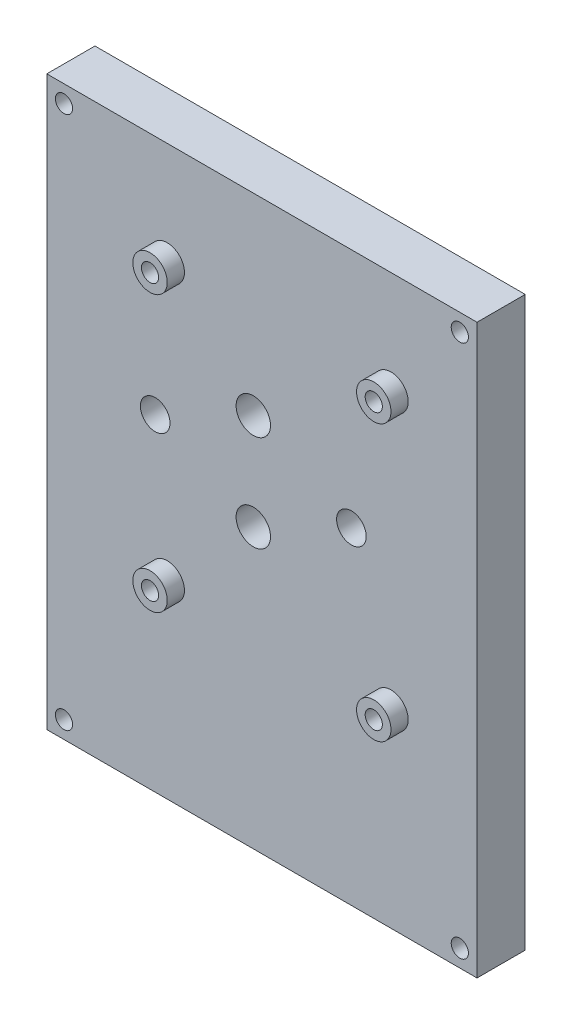
SolidWorks part; units mm, degrees
ref_plane "Oben" through (0, 0, 0) normal (0, 0, 1) x (1, 0, 0)
ref_plane "Vorne" through (0, 0, 0) normal (0, 1, 0) x (1, 0, 0)
ref_plane "Rechts" through (0, 0, 0) normal (1, 0, 0) x (0, 0, -1)
sketch "Skizze1" plane through (0, 0, 0) normal (0, 0, 1) x (1, 0, 0)
  line L0 (0, 17) -> (-7.5, 17)
  line L1 (-7.5, 17) -> (-7.5, -17)
  line L2 (-7.5, -17) -> (17.5, -17)
  line L3 (17.5, -17) -> (17.5, 17)
  line L4 (17.5, 17) -> (0, 17)
  line L5 (-7.5, 17) -> (-17.5, 17)
  line L6 (-17.5, 17) -> (-17.5, -17)
  line L7 (-17.5, -17) -> (-7.5, -17)
  circle A0 centre (14.25, 0) radius 2.15
  circle A1 centre (-14.25, 0) radius 2.15
  circle A2 centre (0, 7) radius 2.5
  circle A3 centre (0, -7) radius 2.5
  point P4 (0, 7)
  point P6 (0, -7)
  dimension "D1" = 4.3
  dimension "D2" = 14.25
  dimension "D14" = 5
  dimension "D15" = 35
  dimension "D3" = 14.25
  dimension "D4" = 7
  dimension "D5" = 7
  dimension "D6" = 10
  dimension "D7" = 7.5
  dimension "D8" = 10
  dimension "D9" = 34
  dimension "D10" = 17.5
  dimension "D11" = 34
  dimension "D12" = 17.5
  dimension "D13" = 25
extrude "Aufsatz-Linear austragen1" add sketch "Skizze1" against normal blind 12 contours A1 | A0 region at (14.25, 0, 0) region at (-14.25, 0, 0)
ref_plane "Ebene1" through (0, 0, 0) normal (0, 0, 1) x (1, 0, 0)
extrude "Aufsatz-Linear austragen3" add sketch "Skizze1<3>" along normal blind 7 contours L6 L7 L1 L5 A1 | L3 L4 L0 L1 L2 A3 A2 A0 | A1 | A0 region at (5.0779, 0, 0) region at (-7.8544, 0, 0) region at (14.25, 0, 0) region at (-14.25, 0, 0)
sketch "Skizze1<3>" plane through (0, 0, 0) normal (0, 0, 1) x (1, 0, 0) same geometry as "Skizze1"
sketch "Skizze4" plane through (0, 0, 7) normal (0, 0, 1) x (1, 0, 0)
  line L0 (-25, 30) -> (-25, -42.5)
  line L1 (-25, -42.5) -> (27.5, -42.5)
  line L2 (27.5, -42.5) -> (27.5, 30)
  line L3 (27.5, 30) -> (-25, 30)
  circle A0 centre (-12.5, -20) radius 2.5
  circle A1 centre (-12.5, -20) radius 1.25
  circle A2 centre (-12.5, 20) radius 1.25
  circle A3 centre (-12.5, 20) radius 2.5
  circle A4 centre (20, 20) radius 1.25
  circle A5 centre (20, 20) radius 2.5
  circle A6 centre (20, -20) radius 1.25
  circle A7 centre (20, -20) radius 2.5
  circle A8 centre (0, 7) radius 2.5 construction
  circle A9 centre (0, 7) radius 2.5
  circle A10 centre (0, -7) radius 2.5 construction
  circle A11 centre (0, -7) radius 2.5
  circle A12 centre (-14.25, 0) radius 2.15 construction
  circle A13 centre (-14.25, 0) radius 2.15
  circle A14 centre (14.25, 0) radius 2.15 construction
  circle A15 centre (14.25, 0) radius 2.15
  point P12 (-26.2002, 27.5472)
  circle M17 centre (0, -7) radius 2.5
  circle M18 centre (0, 7) radius 2.5
  dimension "D1" = 5
  dimension "D2" = 2.5
  dimension "D3" = 20
  dimension "D4" = 20
  dimension "D5" = 12.5
  dimension "D6" = 20
  dimension "D7" = 25
  dimension "D8" = 27.5
  dimension "D9" = 30
  dimension "D10" = 42.5
extrude "Aufsatz-Linear austragen4" add sketch "Skizze4" against normal blind 7 contours M17 | M18 | A15 | L0 L1 L2 L3 | A15 | A13 region at (0, 7, 7) region at (0, -7, 7) region at (14.25, 0, 7)
extrude "Aufsatz-Linear austragen5" add sketch "Skizze4<3>" along normal blind 2.5 contours A3 A2 | A5 A4 | A1 | A0 | A7 | A6 region at (-12.5, -20, 7) region at (-14.9293, 20, 7) region at (17.5707, 20, 7)
sketch "Skizze4<3>" plane through (0, 0, 7) normal (0, 0, 1) x (1, 0, 0) same geometry as "Skizze4"
extrude "Schnitt-Linear austragen1" cut sketch "Skizze4<4>" against normal up to surface (7 mm away) contours A1 | A4 | A6 | A2 region at (-12.5, -20, 7) region at (20, 20, 7) region at (20, -20, 7) up to face at (16.4, 0, 0)
sketch "Skizze4<4>" plane through (0, 0, 7) normal (0, 0, 1) x (1, 0, 0) same geometry as "Skizze4"
extrude "Schnitt-Linear austragen2" cut sketch "Skizze4<5>" against normal up to surface (19 mm away) contours A13 | A15 region at (-14.25, 0, 7) region at (14.25, 0, 7) up to face at (16.4, 0, -12)
sketch "Skizze4<5>" plane through (0, 0, 7) normal (0, 0, 1) x (1, 0, 0) same geometry as "Skizze4"
sketch "Skizze6" plane through (0, 0, 7) normal (0, 0, 1) x (1, 0, 0)
  line L0 (27.5, 30) -> (-25, 30) construction
  line L1 (-30, -47.5) -> (32.5, -47.5)
  line L2 (-30, -47.5) -> (-30, 35)
  line L3 (-30, 35) -> (32.5, 35)
  line L4 (32.5, -47.5) -> (32.5, 35)
  line L5 (-30, -47.5) -> (32.5, 35) construction
  line L6 (-30, 35) -> (32.5, -47.5) construction
  line L7 (27.5, -42.5) -> (27.5, 30) construction
  line L8 (-25, -42.5) -> (27.5, -42.5) construction
  line L9 (-25, 30) -> (-25, -42.5) construction
  line L10 (27.5, 30) -> (-25, 30)
  line L11 (27.5, -42.5) -> (27.5, 30)
  line L12 (-25, -42.5) -> (27.5, -42.5)
  line L13 (-25, 30) -> (-25, -42.5)
  point P4 (1.25, -6.25)
  dimension "D1" = 5
  dimension "D2" = 5
  dimension "D3" = 5
  dimension "D4" = 5
extrude "Aufsatz-Linear austragen6" add sketch "Skizze6" against normal up to surface (7 mm away) up to face at (-11.25, 20, 0)
sketch "Skizze5" plane through (0, 0, 7) normal (0, 0, 1) x (1, 0, 0)
  line L4 (-30, -47.5) -> (32.5, -47.5) construction
  line L5 (-30, 35) -> (-30, -47.5) construction
  line L6 (32.5, -47.5) -> (32.5, 35) construction
  line L7 (32.5, 35) -> (-30, 35) construction
  circle A0 centre (-27.5, 32.5) radius 1.25
  circle A1 centre (-27.5, -45) radius 1.25
  circle A2 centre (30, -45) radius 1.25
  circle A3 centre (30, 32.5) radius 1.25
  point P8 (0, 0)
  point P9 (0, 0)
  point P10 (0, 0)
  point P11 (0, 0)
  point P16 (-24.3301, -48.7215)
  point P17 (0, 0)
  dimension "D1" = 2.5
  dimension "D2" = 2.5
  dimension "D3" = 2.5
  dimension "D4" = 2.5
  dimension "D5" = 2.5
extrude "Schnitt-Linear austragen3" cut sketch "Skizze5" against normal up to surface (7 mm away) contours A0 | A3 | A2 | A1 up to face at (-11.25, 20, 0)
